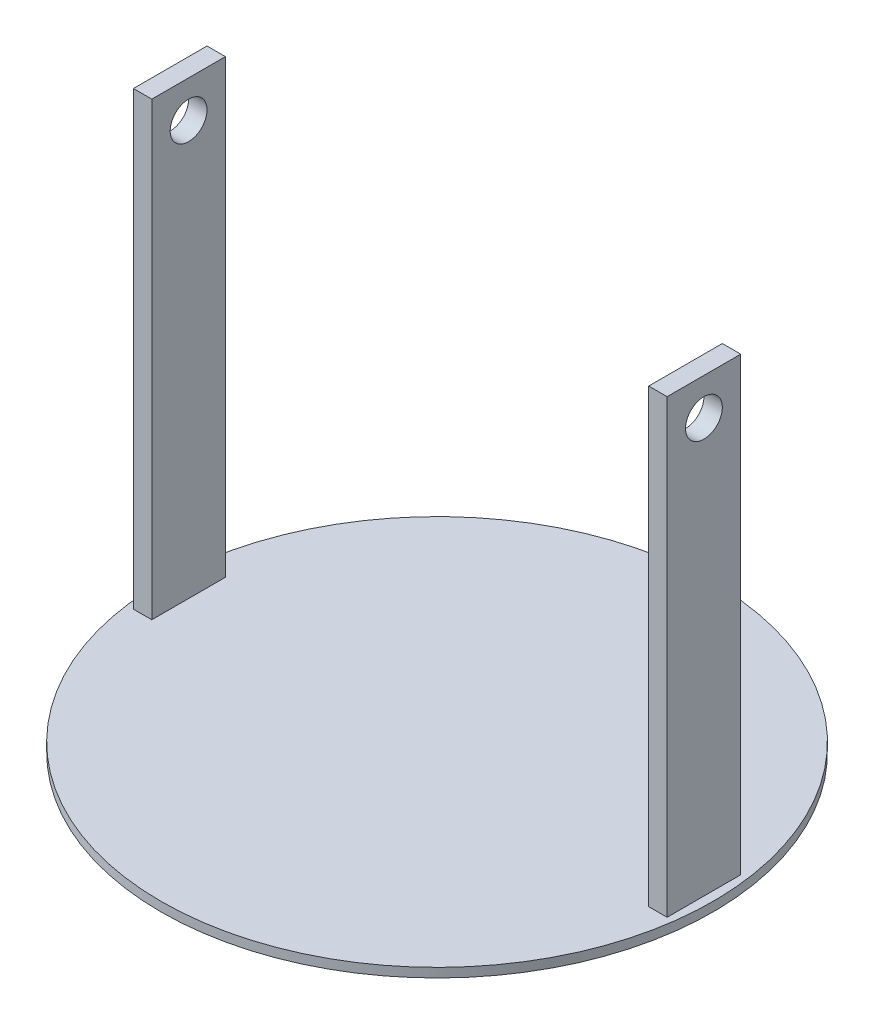
SolidWorks part; units mm, degrees
ref_plane "Front Plane" through (0, 0, 0) normal (0, 0, 1) x (1, 0, 0)
ref_plane "Top Plane" through (0, 0, 0) normal (0, 1, 0) x (1, 0, 0)
ref_plane "Right Plane" through (0, 0, 0) normal (1, 0, 0) x (0, 0, -1)
sketch "Szkic1" plane through (0, 0, 0) normal (0, 1, 0) x (1, 0, 0)
  line L0 (0, 0) -> (140, 0)
  line L1 (140, 0) -> (140, -20)
  line L2 (140, -20) -> (140, 20)
  line L3 (0, 0) -> (-140, 0)
  line L4 (-140, 0) -> (-140, -20)
  line L5 (-140, -20) -> (-140, 20)
  line L7 (145, 20) -> (135, 20)
  line L8 (145, 20) -> (145, -20)
  line L9 (145, -20) -> (135, -20)
  line L10 (135, 20) -> (135, -20)
  line L11 (145, 20) -> (135, -20) construction
  line L12 (145, -20) -> (135, 20) construction
  line L13 (-145, 20) -> (-135, 20)
  line L14 (-145, 20) -> (-145, -20)
  line L15 (-145, -20) -> (-135, -20)
  line L16 (-135, 20) -> (-135, -20)
  line L17 (-145, 20) -> (-135, -20) construction
  line L18 (-145, -20) -> (-135, 20) construction
  circle A0 centre (0, 0) radius 150
  dimension "D1" = 140
  dimension "D9" = 300
  dimension "D2" = 40
  dimension "D3" = 20
  dimension "D4" = 140
  dimension "D5" = 40
  dimension "D6" = 20
  dimension "D7" = 10
  dimension "D8" = 10
extrude "Dodanie-wyciągnięcie1" add sketch "Szkic1" along normal blind 250 contours L16 L15 L14 L13 | L8 L9 L10 L7
extrude "Dodanie-wyciągnięcie2" add sketch "Szkic1<3>" along normal blind 5 contours A0 L13 L16 L10 L7 L8 L9 L15 L14 region at (-145.7574, 0, 0)
sketch "Szkic1<3>" plane through (0, 0, 0) normal (0, 1, 0) x (1, 0, 0) same geometry as "Szkic1"
sketch "Szkic2" plane through (145, 0, 0) normal (1, 0, 0) x (0, 0, -1)
  line L0 (-150, 5) -> (150, 5)
  line L3 (20, 250) -> (20, 5) construction
  line L4 (-20, 250) -> (20, 250) construction
  line L5 (20, 250) -> (20, 210) construction
  circle A0 centre (0, 230) radius 10
  dimension "D3" = 20
  dimension "D1" = 245
  dimension "D2" = 40
extrude "Wytnij-wyciągnięcie1" cut sketch "Szkic2" against normal blind 290 contours A0 region at (145, 230, 0)
sketch "Szkic3" plane through (145, 0, 0) normal (1, 0, 0) x (0, 0, -1)
  line L0 (-20, 250) -> (20, 250) construction
  line L1 (0, 240) -> (0, 250) construction
  line L2 (0, 240) -> (0, 220) construction
  line L3 (0, 230) -> (0, 190) construction
  line L4 (12.36, 190) -> (-12.36, 190)
  line L5 (-12.36, 190) -> (-12.36, 188)
  line L6 (-12.36, 188) -> (12.36, 188)
  line L7 (12.36, 188) -> (12.36, 190)
  circle A0 centre (0, 230) radius 10 construction
  point P16 (0, 190)
  dimension "D1" = 10
  dimension "D2" = 20
  dimension "D3" = 40
  dimension "D4" = 24.72
  dimension "D5" = 2
